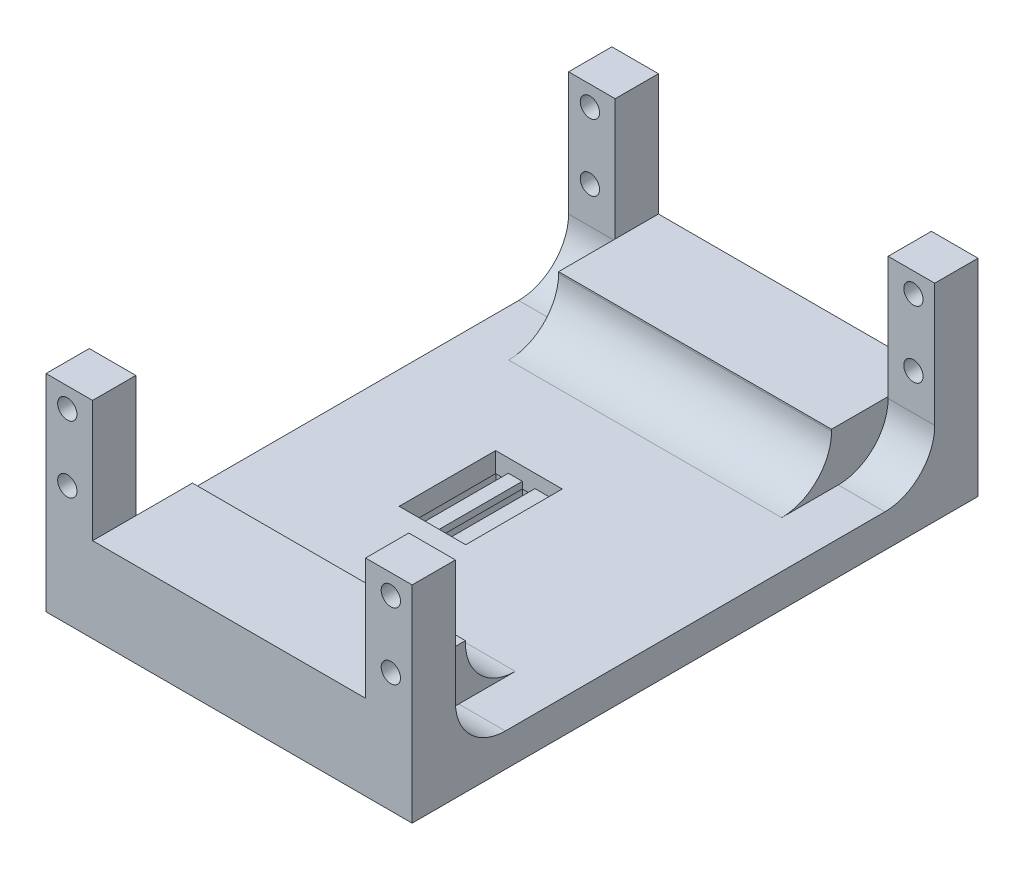
SolidWorks part; units mm, degrees
ref_plane "Спереди" through (0, 0, 0) normal (0, 0, 1) x (1, 0, 0)
ref_plane "Сверху" through (0, 0, 0) normal (0, 1, 0) x (1, 0, 0)
ref_plane "Справа" through (0, 0, 0) normal (1, 0, 0) x (0, 0, -1)
sketch "Эскиз1" plane through (0, 0, 0) normal (0, 1, 0) x (1, 0, 0)
  line L1 (-47.75, 42.5) -> (7.25, 42.5)
  line L2 (-47.75, 42.5) -> (-47.75, -42.5)
  line L3 (-47.75, -42.5) -> (7.25, -42.5)
  line L4 (7.25, 42.5) -> (7.25, -42.5)
  point P4 (7.25, 0)
  dimension "D1" = 55
  dimension "D2" = 85
  dimension "D3" = 7.25
extrude "Бобышка-Вытянуть1" add sketch "Эскиз1" along normal blind 5
sketch "Эскиз2" plane through (0, 5, 0) normal (0, 1, 0) x (1, 0, 0)
  line L0 (-993, 0) -> (49007, 0) construction
  line L1 (-47.75, 42.5) -> (-40.75, 42.5)
  line L2 (-47.75, 42.5) -> (-47.75, 36)
  line L3 (-47.75, 36) -> (-40.75, 36)
  line L4 (-40.75, 42.5) -> (-40.75, 36)
  line L5 (7.25, -42.5) -> (7.25, 42.5) construction
  line L6 (-20.25, -956.862) -> (-20.25, 49043.138) construction
  line L7 (0.25, 42.5) -> (0.25, 36)
  line L8 (7.25, 36) -> (0.25, 36)
  line L9 (7.25, 42.5) -> (7.25, 36)
  line L10 (7.25, 42.5) -> (0.25, 42.5)
  line L11 (7.25, 42.5) -> (-47.75, 42.5) construction
  line L12 (7.25, -42.5) -> (0.25, -42.5)
  line L13 (7.25, -42.5) -> (7.25, -36)
  line L14 (7.25, -36) -> (0.25, -36)
  line L15 (0.25, -42.5) -> (0.25, -36)
  line L16 (-40.75, -42.5) -> (-40.75, -36)
  line L17 (-47.75, -36) -> (-40.75, -36)
  line L18 (-47.75, -42.5) -> (-47.75, -36)
  line L19 (-47.75, -42.5) -> (-40.75, -42.5)
  point P10 (7.25, 0)
  point P16 (-20.25, 42.5)
  point P17 (-20.5, 42.5)
  point P20 (-20.25, -42.5)
  dimension "D1" = 7
  dimension "D2" = 6.5
extrude "Бобышка-Вытянуть2" add sketch "Эскиз2" along normal blind 26
sketch "Эскиз3" plane through (0, 0, 42.5) normal (0, 0, 1) x (1, 0, 0)
  line L1 (-47.75, 31) -> (-40.75, 31) construction
  line L3 (-20.25, -995) -> (-20.25, 49005) construction
  line L4 (-40.75, 5) -> (0.25, 5) construction
  circle A0 centre (-44.55, 28) radius 1.45
  circle A1 centre (-44.55, 18) radius 1.45
  circle A4 centre (4.05, 18) radius 1.45
  circle A5 centre (4.05, 28) radius 1.45
  point P15 (-20.25, 5)
  dimension "D1" = 10
  dimension "D3" = 2.9
  dimension "D2" = 3
  dimension "D4" = 48.6
extrude "Вырез-Вытянуть1" cut sketch "Эскиз3" against normal through all
sketch "Эскиз4" plane through (0, 5, 0) normal (0, 1, 0) x (1, 0, 0)
  line L0 (0.25, 42.5) -> (0.25, 36) construction
  line L1 (-40.75, 42.5) -> (0.25, 42.5)
  line L2 (-40.75, 42.5) -> (-40.75, 27.5)
  line L3 (-40.75, 27.5) -> (0.25, 27.5)
  line L4 (0.25, 42.5) -> (0.25, 27.5)
  line L5 (-1000, 0) -> (49000, 0) construction
  line L6 (0.25, -42.5) -> (0.25, -27.5)
  line L7 (-40.75, -27.5) -> (0.25, -27.5)
  line L8 (-40.75, -42.5) -> (-40.75, -27.5)
  line L9 (-40.75, -42.5) -> (0.25, -42.5)
  dimension "D1" = 15
extrude "Бобышка-Вытянуть3" add sketch "Эскиз4" along normal blind 7.75
sketch "Эскиз5" plane through (0, 0, 0) normal (0, -1, 0) x (1, 0, 0)
  line L0 (-1071.5513, 0) -> (48928.4487, 0) construction
  line L1 (-20.25, -1025.7217) -> (-20.25, 48974.2783) construction
  line L2 (-8, -24.75) -> (-8, 24.75)
  line L3 (-8, -24.75) -> (-32.5, -24.75)
  line L4 (-32.5, -24.75) -> (-32.5, 24.75)
  line L5 (-8, 24.75) -> (-32.5, 24.75)
  line L6 (-8, -24.75) -> (-32.5, 24.75) construction
  line L7 (-32.5, -24.75) -> (-8, 24.75) construction
  line L8 (-47.75, 42.5) -> (7.25, 42.5) construction
  point P3 (-20.25, 0)
  point P14 (-20.25, 42.5)
  dimension "D1" = 24.5
  dimension "D2" = 49.5
extrude "Бобышка-Вытянуть4" add sketch "Эскиз5" along normal blind 10
sketch "Эскиз7" plane through (0, -10, 0) normal (0, -1, 0) x (1, 0, 0)
  line L0 (-8, -24.75) -> (-8, 24.75) construction
  line L1 (-8, -24.75) -> (-8, 24.75) construction
  line L2 (-8, 24.75) -> (-32.5, 24.75) construction
  line L3 (-32.5, -24.75) -> (-8, -24.75) construction
  circle A0 centre (-13, 20) radius 2.525
  circle A1 centre (-13, -20) radius 2.525
  point P10 (-12.8562, -21.0428)
  dimension "D1" = 5
  dimension "D5" = 5.05
  dimension "D2" = 5
  dimension "D3" = 4.75
  dimension "D4" = 4.75
extrude "Вырез-Вытянуть2" cut sketch "Эскиз7" against normal blind 2.25
sketch "Эскиз8" plane through (0, -10, 0) normal (0, -1, 0) x (1, 0, 0)
  line L0 (-1000, 0) -> (49000, 0) construction
  line L13 (-32.5, 24.75) -> (-32.5, -24.75) construction
  line L14 (-30.35, 7.7) -> (-27.65, 7.7)
  line L15 (-30.35, 7.7) -> (-30.35, -7.7)
  line L16 (-30.35, -7.7) -> (-27.65, -7.7)
  line L17 (-27.65, 7.7) -> (-27.65, -7.7)
  line L18 (-26.35, 7.7) -> (-23.65, 7.7)
  line L19 (-26.35, 7.7) -> (-26.35, -7.7)
  line L20 (-26.35, -7.7) -> (-23.65, -7.7)
  line L21 (-23.65, 7.7) -> (-23.65, -7.7)
  point P1 (-23.65, 0)
  dimension "D5" = 2.15
  dimension "D6" = 2.7
  dimension "D7" = 15.4
  dimension "D8" = 4
extrude "Вырез-Вытянуть3" cut sketch "Эскиз8" against normal blind 12
sketch "Эскиз9" plane through (0, 2, 0) normal (0, -1, 0) x (1, 0, 0)
  line L12 (-1030.35, 0) -> (48969.65, 0) construction
  line L13 (-30.35, 7.7) -> (-30.35, -7.7) construction
  line L14 (-29, -992.3) -> (-29, 49007.7) construction
  line L15 (-27.65, 7.7) -> (-30.35, 7.7) construction
  line L16 (-25, -992.3) -> (-25, 49007.7) construction
  line L17 (-23.65, 7.7) -> (-26.35, 7.7) construction
  line L19 (-29.95, -7.25) -> (-28.05, -7.25)
  line L20 (-29.95, -7.25) -> (-29.95, 7.25)
  line L21 (-29.95, 7.25) -> (-28.05, 7.25)
  line L22 (-28.05, -7.25) -> (-28.05, 7.25)
  line L23 (-29.95, -7.25) -> (-28.05, 7.25) construction
  line L24 (-29.95, 7.25) -> (-28.05, -7.25) construction
  line L25 (-25.95, -7.25) -> (-24.05, -7.25)
  line L26 (-25.95, -7.25) -> (-25.95, 7.25)
  line L27 (-25.95, 7.25) -> (-24.05, 7.25)
  line L28 (-24.05, -7.25) -> (-24.05, 7.25)
  line L29 (-25.95, -7.25) -> (-24.05, 7.25) construction
  line L30 (-25.95, 7.25) -> (-24.05, -7.25) construction
  point P15 (-30.35, 0)
  point P20 (-29, 7.7)
  point P21 (-29, 0)
  point P25 (-25, 7.7)
  point P30 (-25, 0)
  dimension "D4" = 1.9
  dimension "D5" = 14.5
extrude "Вырез-Вытянуть4" cut sketch "Эскиз9" against normal blind 1
sketch "Эскиз10" plane through (0, 3, 0) normal (0, -1, 0) x (1, 0, 0)
  line L0 (-29.95, -7.25) -> (-28.05, -7.25) construction
  line L5 (-29.95, 7.25) -> (-19.95, 7.25)
  line L6 (-29.95, 7.25) -> (-29.95, -7.25)
  line L7 (-29.95, -7.25) -> (-19.95, -7.25)
  line L8 (-19.95, 7.25) -> (-19.95, -7.25)
  dimension "D1" = 10
extrude "Вырез-Вытянуть5" cut sketch "Эскиз10" against normal through all
fillet "Скругление1" radius 3 4 edges at (-8, -5, 24.75) (-8, -5, -24.75) (-32.5, -5, -24.75) (-32.5, -5, 24.75)
fillet "Скругление2" radius 7.5 6 edges at (-44.25, 5, -36) (3.75, 5, -36) (-20.25, 5, -27.5) (3.75, 5, 36) (-44.25, 5, 36) (-20.25, 5, 27.5)
